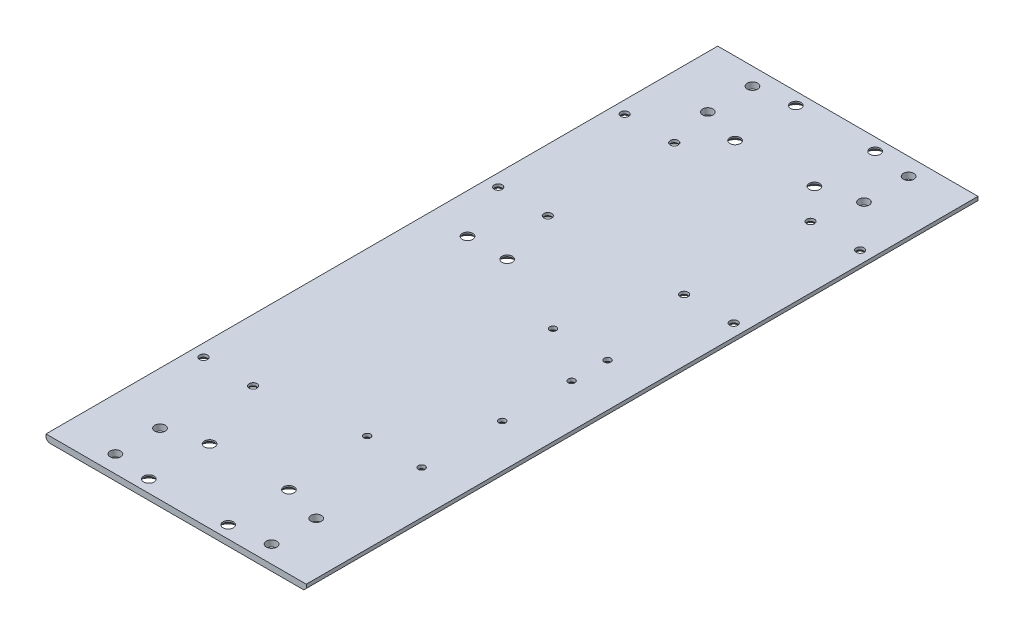
SolidWorks part; units mm, degrees
ref_plane "前视基准面" through (0, 0, 0) normal (0, 0, 1) x (1, 0, 0)
ref_plane "上视基准面" through (0, 0, 0) normal (0, 1, 0) x (1, 0, 0)
ref_plane "右视基准面" through (0, 0, 0) normal (1, 0, 0) x (0, 0, -1)
sketch "草图1" plane through (0, 0, 0) normal (0, 1, 0) x (1, 0, 0)
  line L6 (-52.5, -135.5) -> (52.5, -135.5)
  line L7 (52.5, -135.5) -> (52.5, 135.5)
  line L8 (-52.5, 135.5) -> (52.5, 135.5)
  line L9 (-52.5, -135.5) -> (-52.5, 135.5)
  line L10 (-16, -135.5) -> (-16, -106) construction
  line L11 (0, -55) -> (0, 55) construction
  line L12 (-55, 0) -> (55, 0) construction
  circle A0 centre (16, -130.5) radius 2.1
  circle A1 centre (-16, -130.5) radius 2.1
  circle A2 centre (16, 130.5) radius 2.1
  circle A3 centre (-16, 130.5) radius 2.1
  circle A4 centre (-16, -106) radius 2.1
  circle A5 centre (16, -106) radius 2.1
  circle A6 centre (16, 106) radius 2.1
  circle A7 centre (-16, 106) radius 2.1
  point P8 (-50, 0)
extrude "凸台-拉伸1" add sketch "草图1" along normal blind 2.5
sketch "草图2" plane through (0, 2.5, 0) normal (0, 1, 0) x (1, 0, 0)
  line L0 (0, -1.375) -> (0, 1.375) construction
  line L1 (-1.375, 0) -> (1.375, 0) construction
  circle A0 centre (47.5, 41.95) radius 1.6
  circle A1 centre (27.5, 41.95) radius 1.6
  circle A2 centre (47.5, 92.95) radius 1.6
  circle A3 centre (27.5, 92.95) radius 1.6
  circle A4 centre (-20.5, 18.55) radius 2.1
  circle A5 centre (-36.5, 18.55) radius 2.1
  circle A6 centre (-27.5, -76.95) radius 1.6
  circle A7 centre (-47.5, -76.95) radius 1.6
  circle A8 centre (-27.5, 92.95) radius 1.6
  circle A9 centre (-47.5, 92.95) radius 1.6
  circle A10 centre (-27.5, 41.95) radius 1.6
  circle A11 centre (-47.5, 41.95) radius 1.6
  circle A12 centre (-31.5, 128.5) radius 2.1
  circle A13 centre (-31.5, 110.5) radius 2.1
  circle A14 centre (31.5, 110.5) radius 2.1
  circle A15 centre (31.5, 128.5) radius 2.1
  circle A16 centre (31.5, -128.5) radius 2.1
  circle A17 centre (31.5, -110.5) radius 2.1
  circle A18 centre (-31.5, -110.5) radius 2.1
  circle A19 centre (-31.5, -128.5) radius 2.1
  circle A20 centre (13, 3.55) radius 1.35
  circle A21 centre (35, 3.55) radius 1.35
  circle A22 centre (35, -10.95) radius 1.35
  circle A23 centre (35, -38.95) radius 1.35
  circle A24 centre (35, -71.45) radius 1.35
  circle A25 centre (13, -71.45) radius 1.35
  point P33 (13, 3.55)
  point P40 (35, 3.55)
  point P43 (35, -10.95)
  point P64 (35, -38.95)
  point P67 (35, -71.45)
  point P70 (13, -71.45)
  point P71 (0, 0)
  point P72 (0, 0)
  point P73 (0, 0)
  point P74 (0, 0)
  point P75 (0, 0)
  point P76 (0, 0)
  point P77 (0, 0)
extrude "切除-拉伸1" cut sketch "草图2" against normal blind 10
chamfer "倒角1" distance 1.9 angle 45 10 edges at (-16, 0, -108.1) (-16, 0, -128.4) (16, 0, -103.9) (16, 0, -132.6) (-36.5, 0, -20.65) (-20.5, 0, -20.65) (-16, 0, 128.4) (-16, 0, 108.1) (16, 0, 132.6) (16, 0, 103.9)
chamfer "倒角2" distance 1.4 angle 45 10 edges at (-47.5, 0, 75.35) (-27.5, 0, 75.35) (-47.5, 0, -43.55) (-27.5, 0, -43.55) (27.5, 0, -43.55) (47.5, 0, -43.55) (47.5, 0, -94.55) (27.5, 0, -94.55) (-47.5, 0, -94.55) (-27.5, 0, -94.55)
chamfer "倒角3" distance 1.15 angle 45 6 edges at (13, 0, 70.1) (35, 0, 70.1) (35, 0, 37.6) (35, 0, 9.6) (13, 0, -4.9) (35, 0, -4.9)
chamfer "倒角4" distance 1 angle 45 2 edges at (52.5, 0, 0) (-52.5, 0, 0)
